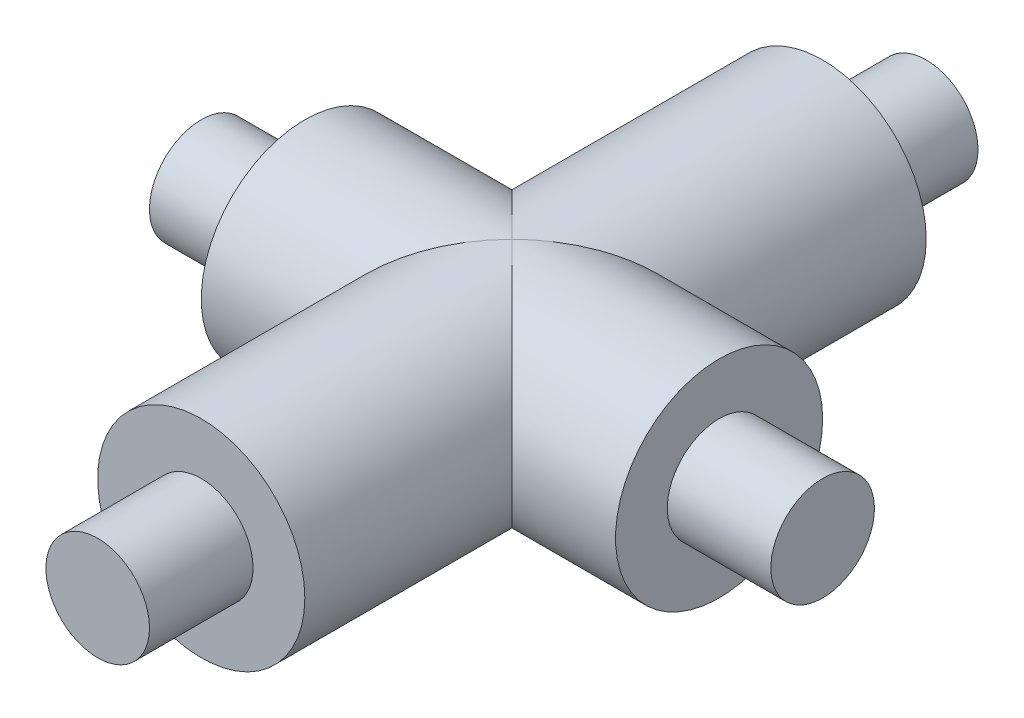
SolidWorks part; units mm, degrees
ref_plane "Front Plane" through (0, 0, 0) normal (0, 0, 1) x (1, 0, 0)
ref_plane "Top Plane" through (0, 0, 0) normal (0, 1, 0) x (1, 0, 0)
ref_plane "Right Plane" through (0, 0, 0) normal (1, 0, 0) x (0, 0, -1)
sketch "Sketch1" plane through (0, 0, 0) normal (0, 0, 1) x (1, 0, 0)
  circle A0 centre (0, 0) radius 5
  dimension "D1" = 10
extrude "Boss-Extrude1" add sketch "Sketch1" against normal blind 30
ref_plane "Plane1" through (0, 0, 0) normal (1, 0, 0) x (0, 0, -1)
sketch "Sketch3" plane through (0, 0, 0) normal (1, 0, 0) x (0, 0, -1)
  line L0 (0, 5) -> (0, -5) construction
  circle A0 centre (15, 0) radius 5
  point P0 (15, 0)
  dimension "D2" = 10
  dimension "D1" = 15
extrude "Boss-Extrude2" add sketch "Sketch3" along normal blind 10 and the other way blind 10
sketch "Sketch5" plane through (10, 0, 0) normal (1, 0, 0) x (0, 0, -1)
  circle A0 centre (15, 0) radius 2.5
  point P0 (15, 0)
  dimension "D2" = 5
  dimension "D1" = 15
extrude "Boss-Extrude3" add sketch "Sketch5" along normal blind 5 and the other way blind 25
sketch "Sketch6" plane through (0, 0, 0) normal (0, 0, 1) x (1, 0, 0)
  circle A0 centre (0, 0) radius 2.5
  dimension "D1" = 5
extrude "Boss-Extrude4" add sketch "Sketch6" along normal blind 5 and the other way blind 35
